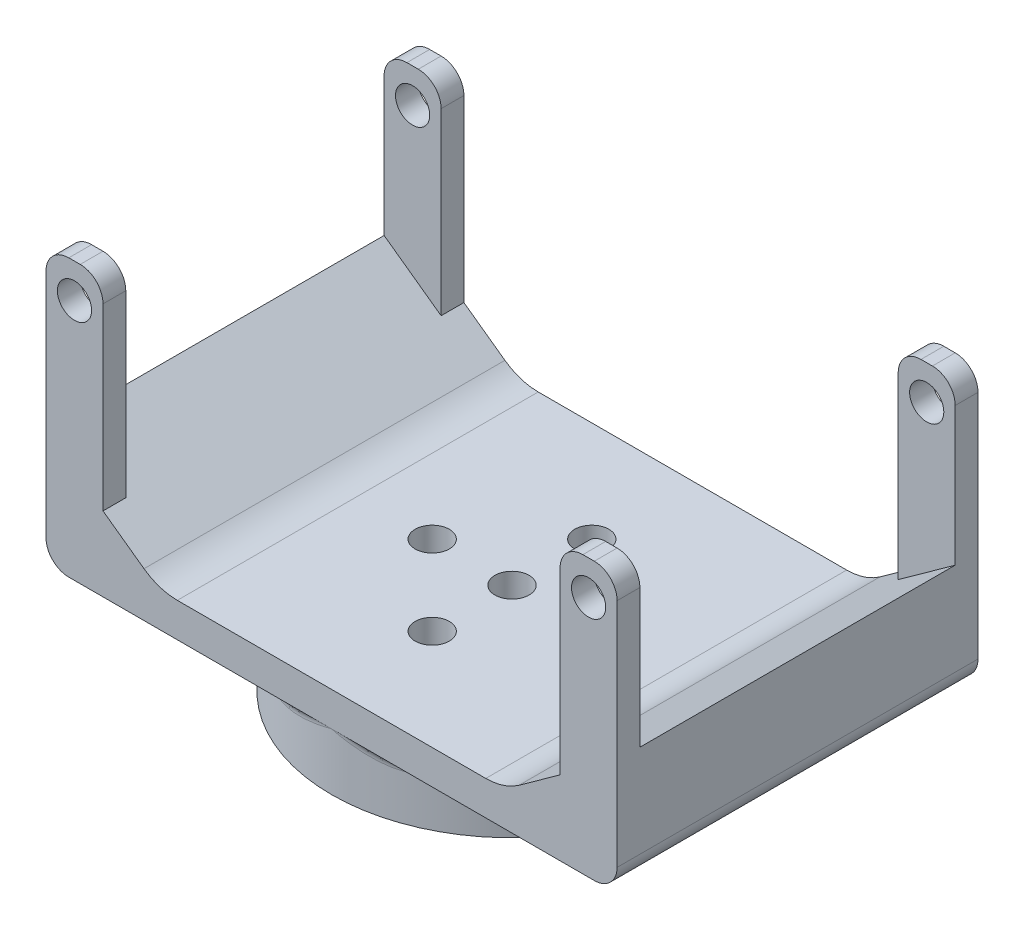
SolidWorks part; units mm, degrees
material "ABS"
ref_plane "Plan de face" through (0, 0, 0) normal (0, 0, 1) x (1, 0, 0)
ref_plane "Plan de dessus" through (0, 0, 0) normal (0, 1, 0) x (1, 0, 0)
ref_plane "Plan de droite" through (0, 0, 0) normal (1, 0, 0) x (0, 0, -1)
sketch "Esquisse1" plane through (0, 0, 0) normal (0, 0, 1) x (1, 0, 0)
  line B0 (-22.0488, -2.891) -> (-23.0488, -2.891)
  line B1 (-25.0488, -4.891) -> (-25.0488, -25.1527)
  line B2 (-23.0488, -27.1527) -> (23.0488, -27.1527)
  line B3 (20.0488, -4.891) -> (20.0488, -20.6213)
  line B4 (-20.0488, -4.891) -> (-20.0488, -20.6213)
  line B5 (25.0488, -4.891) -> (25.0488, -25.1527)
  line B6 (22.0488, -2.891) -> (23.0488, -2.891)
  line B7 (20.0488, -20.6213) -> (16.4505, -23.211)
  line B8 (0, -27.1527) -> (0, -8.6743) construction
  line B9 (25.0488, -17.0229) -> (16.4505, -23.211) construction
  line B10 (-25.0488, -17.0229) -> (-16.4505, -23.211) construction
  line B11 (-20.0488, -20.6213) -> (-16.4505, -23.211)
  line B12 (13.5298, -24.1527) -> (-13.5298, -24.1527)
  arc B13 (-22.0488, -2.891) -> (-20.0488, -4.891) centre (-22.0488, -4.891) cw
  arc B14 (-23.0488, -2.891) -> (-25.0488, -4.891) centre (-23.0488, -4.891) ccw
  arc B15 (-25.0488, -25.1527) -> (-23.0488, -27.1527) centre (-23.0488, -25.1527) ccw
  arc B16 (25.0488, -25.1527) -> (23.0488, -27.1527) centre (23.0488, -25.1527) cw
  arc B17 (23.0488, -2.891) -> (25.0488, -4.891) centre (23.0488, -4.891) cw
  arc B18 (22.0488, -2.891) -> (20.0488, -4.891) centre (22.0488, -4.891) ccw
  arc B19 (-16.4505, -23.211) -> (-13.5298, -24.1527) centre (-13.5298, -19.1527) ccw
  arc B20 (16.4505, -23.211) -> (13.5298, -24.1527) centre (13.5298, -19.1527) cw
sketch_block_instance "Bloc6-1"
sketch_block "Bloc6" parameters "D3"=2, "D4"=5, "D1"=3, "D2"=5
extrude "Boss.-Extru.1" add sketch "Esquisse1" along normal blind 2
sketch "Esquisse2" plane through (0, 0, 2) normal (0, 0, 1) x (1, 0, 0)
  line L0 (13.5298, -24.1527) -> (-13.5298, -24.1527) construction
  line L1 (25.0488, -17.0229) -> (16.4505, -23.211) construction
  line L2 (25.0488, -4.891) -> (25.0488, -25.1527) construction
  line L3 (-23.0488, -27.1527) -> (23.0488, -27.1527) construction
  line L4 (-25.0488, -4.891) -> (-25.0488, -25.1527) construction
  line L5 (-25.0488, -17.0229) -> (-16.4505, -23.211) construction
  line L6 (13.5298, -24.1527) -> (-13.5298, -24.1527)
  line L7 (25.0488, -17.0229) -> (16.4505, -23.211)
  line L8 (25.0488, -17.0229) -> (25.0488, -25.1527)
  line L9 (-23.0488, -27.1527) -> (23.0488, -27.1527)
  line L10 (-25.0488, -17.0229) -> (-25.0488, -25.1527)
  line L11 (-25.0488, -17.0229) -> (-16.4505, -23.211)
  arc A0 (-16.4505, -23.211) -> (-13.5298, -24.1527) centre (-13.5298, -19.1527) ccw construction
  arc A1 (13.5298, -24.1527) -> (16.4505, -23.211) centre (13.5298, -19.1527) ccw construction
  arc A2 (23.0488, -27.1527) -> (25.0488, -25.1527) centre (23.0488, -25.1527) ccw construction
  arc A3 (-25.0488, -25.1527) -> (-23.0488, -27.1527) centre (-23.0488, -25.1527) ccw construction
  arc A4 (-16.4505, -23.211) -> (-13.5298, -24.1527) centre (-13.5298, -19.1527) ccw
  arc A5 (13.5298, -24.1527) -> (16.4505, -23.211) centre (13.5298, -19.1527) ccw
  arc A6 (23.0488, -27.1527) -> (25.0488, -25.1527) centre (23.0488, -25.1527) ccw
  arc A7 (-25.0488, -25.1527) -> (-23.0488, -27.1527) centre (-23.0488, -25.1527) ccw
extrude "Boss.-Extru.2" add sketch "Esquisse2" along normal blind 13.83
mirror "Symétrie1" about plane through (-13.5298, -19.1527, 15.83) normal (0, 0, 1) of bodies 102
sketch "Esquisse3" plane through (0, 0, 31.66) normal (0, 0, 1) x (1, 0, 0)
  line L0 (-25.0488, -4.891) -> (-25.0488, -25.1527) construction
  line L1 (-22.0488, -2.891) -> (-23.0488, -2.891) construction
  circle A0 centre (-22.5488, -5.891) radius 1.5
  dimension "D2" = 3
  dimension "D1" = 2.5
  dimension "D3" = 3
extrude "Enlèv. mat.-Extru.1" cut sketch "Esquisse3" against normal through all
mirror "Symétrie2" about plane through (0, 0, 0) normal (1, 0, 0) of "Enlèv. mat.-Extru.1"
sketch "Esquisse4" plane through (0, -27.1527, 0) normal (0, -1, 0) x (1, 0, 0)
  line L0 (23.0488, 31.66) -> (-23.0488, 0) construction
  line L1 (-23.0488, 31.66) -> (23.0488, 0) construction
  circle A0 centre (0, 15.83) radius 1.5
  circle A1 centre (0, 22.83) radius 1.5
  circle A2 centre (7, 15.83) radius 1.5
  circle A3 centre (0, 8.83) radius 1.5
  circle A4 centre (-7, 15.83) radius 1.5
  point P21 (0, 15.83)
  dimension "D1" = 3
  dimension "D2" = 3
  dimension "D3" = 7
  dimension "D4" = 4
extrude "Enlèv. mat.-Extru.2" cut sketch "Esquisse4" against normal blind 3
sketch "Esquisse5" plane through (0, -27.1527, 0) normal (0, -1, 0) x (1, 0, 0)
  circle A0 centre (0, 15.83) radius 15.83
  circle A1 centre (0, 15.83) radius 15
  dimension "D1" = 30
extrude "Boss.-Extru.3" add sketch "Esquisse5" along normal blind 5
fillet "Congé1" radius 1 2 edges at (15.83, -27.1527, 15.83) (-15.83, -27.1527, 15.83)
